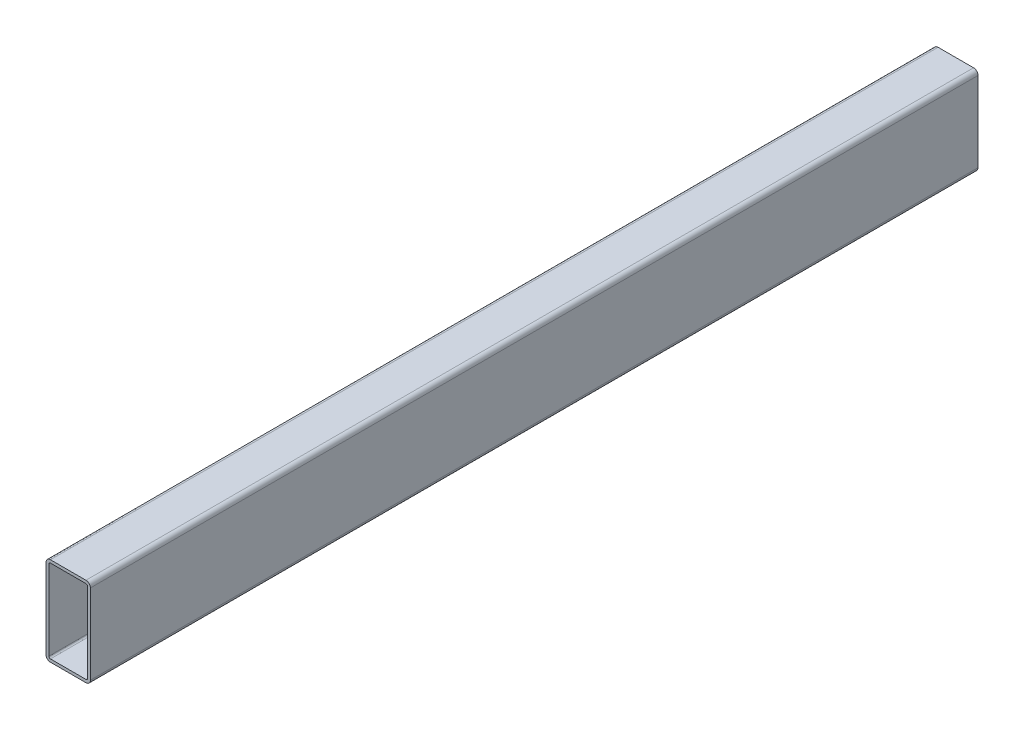
SolidWorks part; units mm, degrees
ref_plane "Front Plane" through (0, 0, 0) normal (0, 0, 1) x (1, 0, 0)
ref_plane "Top Plane" through (0, 0, 0) normal (0, 1, 0) x (1, 0, 0)
ref_plane "Right Plane" through (0, 0, 0) normal (1, 0, 0) x (0, 0, -1)
sketch "Sketch1" plane through (0, 0, 0) normal (0, 0, 1) x (1, 0, 0)
  line L1 (10.16, -25.4) -> (-10.16, -25.4)
  line L2 (12.7, -22.86) -> (12.7, 22.86)
  line L3 (10.16, 25.4) -> (-10.16, 25.4)
  line L4 (-12.7, -22.86) -> (-12.7, 22.86)
  line L5 (12.7, -25.4) -> (-12.7, 25.4) construction
  line L6 (12.7, 25.4) -> (-12.7, -25.4) construction
  arc A0 (-10.16, -25.4) -> (-12.7, -22.86) centre (-10.16, -22.86) cw
  arc A1 (10.16, -25.4) -> (12.7, -22.86) centre (10.16, -22.86) ccw
  arc A2 (12.7, 22.86) -> (10.16, 25.4) centre (10.16, 22.86) ccw
  arc A3 (-10.16, 25.4) -> (-12.7, 22.86) centre (-10.16, 22.86) ccw
  point P0 (0, 0)
  dimension "D3" = 2.54
  dimension "D1" = 25.4
  dimension "D2" = 50.8
extrude "Extrude-Thin1" add sketch "Sketch1" along normal blind 508 thin thin type one direction reverse wall 1.651
